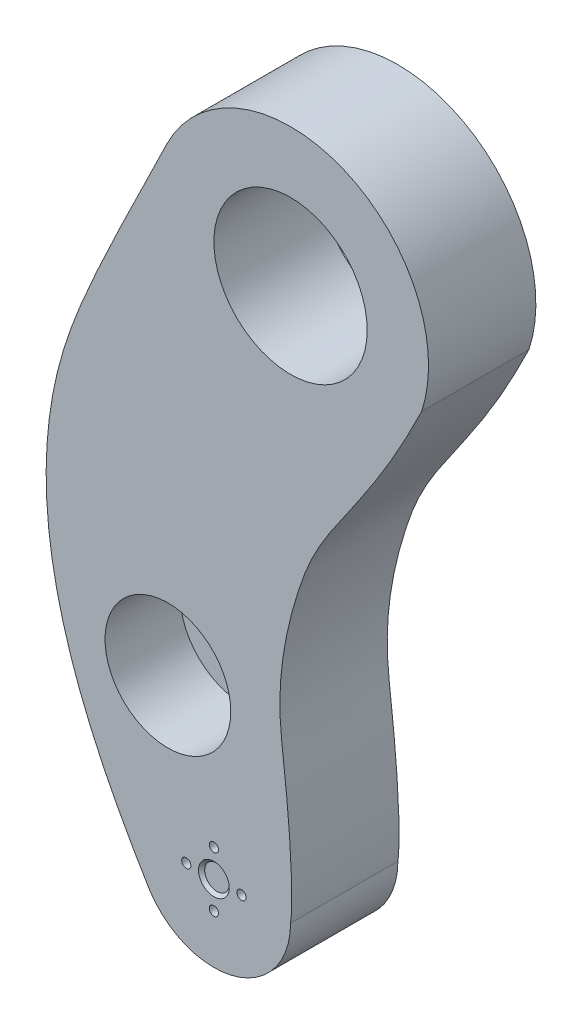
SolidWorks part; units mm, degrees
ref_plane "Ebene vorne" through (0, 0, 0) normal (0, 0, 1) x (1, 0, 0)
ref_plane "Ebene oben" through (0, 0, 0) normal (0, 1, 0) x (1, 0, 0)
ref_plane "Ebene rechts" through (0, 0, 0) normal (1, 0, 0) x (0, 0, -1)
sketch "Skizze1" plane through (0, 0, 0) normal (0, 0, 1) x (1, 0, 0)
  circle A0 centre (0, 0) radius 9
  circle A6 centre (0, 0) radius 25
  circle A7 centre (25, 180) radius 45
  circle A8 centre (25, 180) radius 25
  spline S0 degree 3 poles (-15.2208, 200.1813) (-37.2573, 155.4099) (-73.4434, 79.5174) (-38.6711, 15.7685) (-20.9233, -13.6827) knots 0 0 0 0 0.231883 1 1 1 1
  spline S1 degree 3 poles (67.7341, 165.9004) (51.1385, 131.5089) (36.2521, 119.622) (25.0061, 88.4676) (20.0361, 66.2697) (25.6637, 21.506) (25.7093, 4.904) (25, 0) knots 0 0 0 0 0.347734 0.409135 0.591244 0.652607 1 1 1 1
  point P14 (0, 0)
  dimension "D1" = 18
  dimension "D3" = 50
  dimension "D5" = 90
  dimension "D7" = 50
  dimension "D4" = 180
  dimension "D6" = 25
extrude "Aufsatz-Linear austragen1" add sketch "Skizze1" along normal blind 35 contours S1 A7 S0 | S1 A7 S0 A6 | A6 S0 A0 | A0 region at (0, 0, 0) region at (-20.8092, -12.5008, 0) region at (-11.7098, 87.9057, 0) region at (2.5666, 142.4659, 0)
sketch "Skizze2" plane through (0, 0, 35) normal (0, 0, 1) x (1, 0, 0)
  circle A0 centre (0, 0) radius 4
  dimension "D1" = 8
extrude "Schnitt-Linear austragen1" cut sketch "Skizze2" against normal blind 1 contours A0
chamfer "Fase1" distance 1 angle 45 1 edges at (4, 0, 35)
sketch "Skizze3" plane through (0, 0, 35) normal (0, 0, 1) x (1, 0, 0)
sketch "Skizze4" plane through (0, 0, 35) normal (0, 0, 1) x (1, 0, 0)
  arc A0 (-1.4948, 8.875) -> (-8.875, 1.4948) centre (0, 0) ccw
  circle A1 centre (9, 0) radius 1.5
  circle A2 centre (0, -9) radius 1.5
  circle A3 centre (-9, 0) radius 1.5
  circle A4 centre (0, 9) radius 1.5
  arc A5 (-8.875, -1.4948) -> (-1.4948, -8.875) centre (0, 0) ccw
  arc A6 (8.875, 1.4948) -> (1.4948, 8.875) centre (0, 0) ccw
  arc A7 (1.4948, -8.875) -> (8.875, -1.4948) centre (0, 0) ccw
  point P14 (0, 0)
  dimension "D1" = 18
  dimension "D2" = 4
extrude "Schnitt-Linear austragen2" cut sketch "Skizze4" against normal blind 15 contours A4 | A1 | A2 | A3 region at (0, 9, 35) region at (-9, 0, 35) region at (9, 0, 35) region at (0, -9, 35)
sketch "Skizze5" plane through (0, 0, 0) normal (0, 0, -1) x (-1, 0, 0)
  circle A0 centre (0, 0) radius 8
  circle A1 centre (8, 0) radius 1.5
  circle A2 centre (0, -8) radius 1.5
  circle A3 centre (-8, 0) radius 1.5
  circle A4 centre (0, 8) radius 1.5
  circle A5 centre (0, 0) radius 9.5
  point P14 (0, 0)
  dimension "D1" = 4
  dimension "D2" = 19
extrude "Schnitt-Linear austragen3" cut sketch "Skizze5" against normal blind 15 contours A0 A4 | A0 A4 | A0 A3 | A0 A3 | A0 A1 | A0 A1 | A0 A2 | A0 A2 region at (-7.3387, 0, 0) region at (-8.6106, 0, 0) region at (0, 7.3387, 0) region at (0, 8.6106, 0) region at (0, -8.6106, 0) region at (0, -7.3387, 0) region at (7.3387, 0, 0) region at (8.6106, 0, 0)
sketch "Skizze6" plane through (0, 0, 35) normal (0, 0, 1) x (1, 0, 0)
  line L0 (-49.7352, 50) -> (22.1206, 50) construction
  circle A1 centre (-15, 50) radius 12.5
  spline S0 degree 3 poles (-15.2208, 200.1813) (-37.2573, 155.4099) (-73.4434, 79.5174) (-38.6711, 15.7685) (-20.9233, -13.6827) knots 0 0 0 0 0.231883 1 1 1 1 construction
  spline S1 degree 3 poles (67.7341, 165.9004) (51.1385, 131.5089) (36.2521, 119.622) (25.0061, 88.4676) (20.0361, 66.2697) (25.6637, 21.506) (25.7093, 4.904) (25, 0) knots 0 0 0 0 0.347734 0.409135 0.591244 0.652607 1 1 1 1 construction
  dimension "D1" = 50
  dimension "D2" = 25
  dimension "D3" = 15
extrude "Schnitt-Linear austragen4" cut sketch "Skizze6" against normal blind 35
sketch "Skizze7" plane through (0, 0, 35) normal (0, 0, 1) x (1, 0, 0)
  circle A0 centre (-15, 50) radius 20.5
  dimension "D1" = 41
extrude "Schnitt-Linear austragen5" cut sketch "Skizze7" against normal offset from surface (24.5 mm away) 10.5 up to face at (-2.5, 50, 0)
sketch "Skizze8" plane through (0, 0, 10.5) normal (0, 0, 1) x (1, 0, 0)
  line L0 (-15, 50) -> (-13.8879, 32.5354) construction
  arc A0 (-18.0975, 67.2237) -> (-32.4775, 50.8878) centre (-15, 50) ccw
  circle A1 centre (-13.8879, 32.5354) radius 2
  circle A2 centre (-32.4646, 48.8879) radius 2
  circle A3 centre (-16.1121, 67.4646) radius 2
  circle A4 centre (2.4646, 51.1121) radius 2
  arc A5 (2.2237, 53.0975) -> (-14.1122, 67.4775) centre (-15, 50) ccw
  arc A6 (-11.9025, 32.7763) -> (2.2237, 53.0975) centre (-15, 50) ccw
  arc A7 (-32.4775, 50.8878) -> (-15.8878, 32.5225) centre (-15, 50) ccw
  point P14 (-15, 50)
  dimension "D1" = 4
  dimension "D2" = 4
  dimension "D3" = 17.5
extrude "Schnitt-Linear austragen6" cut sketch "Skizze8" against normal blind 15 contours A4 | A3 | A1 | A2 | A2 | A4 region at (-16.1121, 67.4646, 10.5) region at (-31.5973, 48.9431, 10.5) region at (1.5973, 51.0569, 10.5) region at (-13.8879, 32.5354, 10.5)
sketch "Skizze9" plane through (0, 0, 0) normal (0, 0, -1) x (-1, 0, 0)
  circle A0 centre (13.8879, 32.5354) radius 3.5
  circle A1 centre (-2.4646, 51.1121) radius 3.5
  circle A2 centre (16.1121, 67.4646) radius 3.5
  circle A3 centre (32.4646, 48.8879) radius 3.5
  point P3 (15, 50)
  point P4 (15.2537, 60)
  point P14 (15, 50)
  dimension "D1" = 7
  dimension "D2" = 4
extrude "Schnitt-Linear austragen7" cut sketch "Skizze9" against normal blind 5
